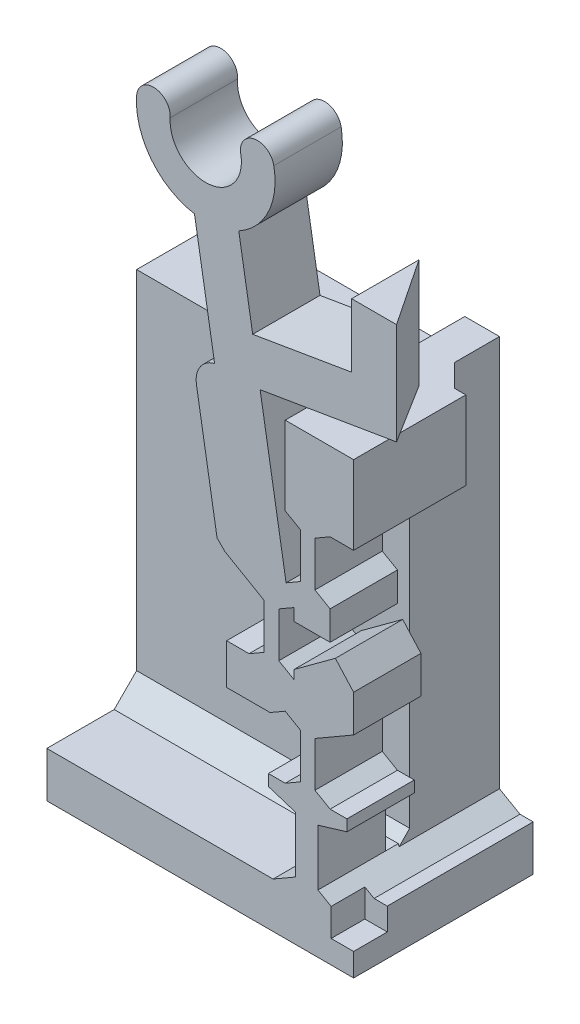
SolidWorks part; units mm, degrees
ref_plane "Front Plane" through (0, 0, 0) normal (0, 0, 1) x (1, 0, 0)
ref_plane "Top Plane" through (0, 0, 0) normal (0, 1, 0) x (1, 0, 0)
ref_plane "Right Plane" through (0, 0, 0) normal (1, 0, 0) x (0, 0, -1)
sketch "Sketch-SkeletonConfigUp" plane through (0, 0, 0) normal (0, 0, 1) x (1, 0, 0)
  line L0 (0, 0) -> (0, -50000) construction
  line L1 (0, 0) -> (4.5811, 6.2164) construction
  line L2 (9.8143, 13.3177) -> (4.5811, 13.945) construction
  line L3 (4.5811, 13.945) -> (2.9713, 10.4094) construction
  line L4 (2.9713, 10.4094) -> (4.5811, 6.2164) construction
  line L5 (4.5811, 13.945) -> (6.2429, 19.1409) construction
  line L6 (2.9713, 10.4094) -> (0.0405, 27.8193) construction
  line L7 (4.5811, 6.2164) -> (9.8143, 13.3177) construction
  line L8 (-587.3593, -797.0242) -> (9.8143, 13.3177) construction
  dimension "D2" = 7.7221
  dimension "D3" = 8.8212
  dimension "D4" = 5.2707
  dimension "D5" = 119.553
  dimension "D6" = 3.8848
  dimension "D7" = 5.4552
  dimension "D8" = 17.6549
  dimension "D9" = 4.4914
  dimension "D10" = 6.745
  dimension "D11" = 145.964
  dimension "D12" = 143.612
sketch "Sketch-SkeletonConfigDown" plane through (0, 0, 0) normal (0, 0, 1) x (1, 0, 0)
  line L0 (0, 0) -> (0, -50000) construction
  line L1 (0, 0) -> (4.5811, 6.2164) construction
  line L2 (9.8143, 13.3177) -> (4.5811, 13.945) construction
  line L3 (4.5811, 13.945) -> (6.1909, 10.4094) construction
  line L4 (6.1909, 10.4094) -> (4.5811, 6.2164) construction
  line L5 (4.5811, 13.945) -> (1.753, 18.6098) construction
  line L6 (6.1909, 10.4094) -> (-8.8652, 19.6294) construction
  line L7 (4.5811, 6.2164) -> (9.8143, 13.3177) construction
  line L8 (-589.9357, -800.5203) -> (9.8143, 13.3177) construction
  dimension "D2" = 7.7221
  dimension "D3" = 8.8212
  dimension "D4" = 5.2707
  dimension "D5" = 119.553
  dimension "D6" = 3.8848
  dimension "D7" = 5.4552
  dimension "D8" = 17.6549
  dimension "D9" = 4.4914
  dimension "D10" = 6.745
  dimension "D11" = 145.964
  dimension "D1" = 143.612
ref_plane "Plane-Cam Base" through (9.128, 0, 0) normal (1, 0, 0) x (0, 0, -1)
ref_plane "Plane-Down-to-Up Derailleur Clearance" through (6.628, 0, 0) normal (1, 0, 0) x (0, 0, -1)
ref_plane "Plane-Cam Cavity Roof" through (5.128, 0, 0) normal (1, 0, 0) x (0, 0, -1)
sketch "Sketch-SwitchBossUp" plane through (0, 0, 0) normal (0, 0, 1) x (1, 0, 0)
  line L0 (3.5811, 11.4759) -> (3.5811, 12.945) construction
  line L2 (6.5405, 22.165) -> (6.5405, 25.0005)
  line L3 (6.5405, 25.0005) -> (8.5405, 25.0005)
  line L4 (8.5405, 25.0005) -> (8.5405, 20.4736)
  line L5 (5.5811, 12.5552) -> (5.5811, 11.263)
  line L7 (1.5115, 25.1048) -> (2.1313, 21.4228)
  line L8 (-0.4607, 24.7728) -> (0.4359, 19.4465)
  line L9 (2.9713, 10.4094) -> (0.0405, 27.8193) construction
  line L11 (-0.0396, 22.2712) -> (1.9326, 22.6032) construction
  line L15 (6.628, -23.7286) -> (6.628, 23.7286) construction
  line L16 (2.9713, 10.4094) -> (4.5811, 6.2164) construction
  line L17 (3.5811, 12.945) -> (3.5811, 14.945) construction
  line L18 (5.5811, 12.945) -> (5.5811, 14.945) construction
  line L19 (4.2561, 13.945) -> (4.9061, 13.945) construction
  line L20 (3.5811, 14.945) -> (5.5811, 14.945) construction
  line L21 (3.5811, 12.945) -> (5.5811, 12.945) construction
  line L22 (4.5811, 12.945) -> (4.5811, 14.945) construction
  line L23 (4.5811, 6.2164) -> (8.5405, 7.1023) construction
  line L24 (1.9713, 9.4094) -> (1.9713, 11.4094) construction
  line L25 (3.9713, 9.4094) -> (3.9713, 11.4094) construction
  line L26 (3.9713, 9.4094) -> (1.9713, 9.4094) construction
  line L27 (1.9713, 11.4094) -> (3.9713, 11.4094) construction
  line L28 (3.5811, 7.2164) -> (5.5811, 7.2164) construction
  line L29 (3.5811, 7.2164) -> (3.5811, 5.2164) construction
  line L30 (5.5811, 7.2164) -> (5.5811, 5.2164) construction
  line L31 (3.5811, 5.2164) -> (5.5811, 5.2164) construction
  line L32 (4.9061, 6.2164) -> (4.2561, 6.2164) construction
  line L40 (3.2963, 10.4094) -> (2.6463, 10.4094) construction
  line L43 (2.874, 4.5093) -> (0.7934, 4.5093) construction
  line L46 (5.0405, 1.437) -> (5.0405, 3.937)
  line L51 (6.5405, 22.165) -> (2.1313, 21.4228)
  line L66 (0.0405, 27.8193) -> (0.0405, 50027.8193) construction
  line L74 (0.5455, 12.7717) -> (-0.3728, 18.2264)
  line L75 (0.3841, 13.7302) -> (2.3564, 14.0622) construction
  line L76 (5.5811, 11.263) -> (5.5811, 12.5552) construction
  line L77 (5.5811, 7.6061) -> (6.628, 8.2105)
  line L80 (5.8152, 10.763) -> (6.628, 9.8603)
  line L81 (8.5405, 7.9632) -> (8.5405, -49992.0368) construction
  line L82 (2.1313, 21.4228) -> (3.5585, 12.945) construction
  line L83 (3.6203, 12.5779) -> (2.4634, 19.4505)
  line L84 (2.4634, 19.4505) -> (8.5405, 20.4736)
  line L85 (6.9307, 9.5241) -> (8.5405, 7.7363) construction
  line L88 (3.5811, 18.8347) -> (6.8573, 18.8347)
  line L92 (3.7762, 8.3129) -> (6.9307, 9.5241) construction
  line L93 (6.3311, 4.3267) -> (5.0405, 3.937)
  line L95 (2.1313, 21.4228) -> (2.4634, 19.4505) construction
  line L96 (2.2974, 20.4367) -> (8.5405, 21.4876) construction
  line L97 (2.2974, 20.4367) -> (1.3112, 20.2707) construction
  line L98 (1.9713, 9.0197) -> (0.9713, 9.0197)
  line L99 (0.9713, 9.0197) -> (0.9713, 7.2164)
  line L100 (0.9713, 7.2164) -> (2.9061, 7.2164)
  line L101 (4.5811, 6.2164) -> (6.9307, 9.5241) construction
  line L104 (6.9307, 9.5241) -> (8.5405, 7.7363) construction
  line L106 (15.3091, 14.945) -> (5.5811, 14.945) construction
  line L107 (1.9713, 9.4094) -> (1.9713, 9.0197) construction
  line L111 (6.628, 9.8603) -> (6.628, 8.2105)
  line L112 (6.628, 9.8603) -> (6.9307, 9.5241) construction
  line L113 (2.8311, 4.8267) -> (2.8311, 4.3267)
  line L114 (7.3693, 7.7363) -> (7.3563, 7.7363) construction
  line L115 (6.8573, 18.8347) -> (15.3091, 18.8347)
  line L116 (15.3091, 18.8347) -> (15.3091, -1.1653)
  line L117 (15.3091, -1.1653) -> (5.0405, -1.1653)
  line L119 (10.4375, 14.0252) -> (10.4375, 2.1692)
  line L121 (5.0405, -1.1653) -> (5.0405, 1.437) construction
  line L122 (10.1044, 15.3031) -> (12.7068, 15.3031) construction
  line L123 (12.7068, 15.3031) -> (15.3091, 15.3031) construction
  line L124 (10.4375, 2.1692) -> (9.128, 0.8597)
  line L125 (8.5405, 8.8347) -> (15.3091, 8.8347) construction
  line L127 (5.5811, 15.3347) -> (5.5811, 14.945) construction
  line L130 (6.0405, 0.8597) -> (9.128, 0.8597)
  line L132 (2.8311, 4.3267) -> (4.0405, 3.937)
  line L133 (2.9713, 10.4094) -> (6.1909, 10.4094) construction
  line L134 (4.5811, 10.4094) -> (4.5811, 13.945) construction
  line L135 (4.5811, 10.4094) -> (4.5811, 6.2164) construction
  line L136 (0.8973, 12.4192) -> (0.5455, 12.7717)
  line L137 (3.9713, 9.4094) -> (5.5811, 7.2164) construction
  line L139 (5.8152, 10.763) -> (3.9713, 9.4094)
  line L140 (4.0405, 3.937) -> (4.0405, 1.437)
  line L141 (4.0405, 1.437) -> (3.0405, 0.8597)
  line L142 (3.0405, 0.8597) -> (3.0405, -1.1653)
  line L147 (5.5811, 11.263) -> (5.5811, 12.5552) construction
  line L149 (6.3311, 4.8267) -> (6.3311, 4.3267)
  line L150 (3.0405, -1.1653) -> (5.0405, -1.1653)
  line L151 (4.0405, 3.937) -> (5.0405, 3.937) construction
  line L152 (4.2561, 14.945) -> (4.2561, 12.945)
  line L153 (4.9061, 14.945) -> (4.9061, 12.945)
  line L155 (4.2561, 14.945) -> (3.5811, 15.3347)
  line L156 (4.9061, 14.945) -> (5.5811, 15.3347)
  line L157 (3.5811, 18.8347) -> (3.5811, 15.3347)
  line L158 (5.5811, 15.3347) -> (9.128, 15.3347)
  line L162 (3.2963, 11.4094) -> (3.2963, 9.4094)
  line L164 (2.6463, 11.4094) -> (2.6463, 9.4094)
  line L169 (4.2561, 7.2164) -> (4.2561, 5.2164)
  line L170 (4.9061, 5.2164) -> (4.9061, 7.2164)
  line L175 (4.2561, 7.2164) -> (3.5811, 7.6061)
  line L176 (4.9061, 7.2164) -> (5.5811, 7.6061)
  line L177 (5.5811, 7.2164) -> (5.5811, 7.6061) construction
  line L179 (4.2561, 5.2164) -> (3.5811, 4.8267)
  line L180 (3.5811, 5.2164) -> (3.5811, 4.8267) construction
  line L181 (3.5811, 4.8267) -> (2.8311, 4.8267)
  line L183 (4.9061, 5.2164) -> (5.5811, 4.8267)
  line L184 (5.5811, 5.2164) -> (5.5811, 4.8267) construction
  line L186 (9.128, -23.7286) -> (9.128, 23.7286) construction
  line L187 (2.6463, 9.4094) -> (1.9713, 9.0197)
  line L188 (3.2963, 9.4094) -> (3.9713, 9.0197)
  line L189 (3.2963, 11.4094) -> (3.9713, 11.7991)
  line L190 (2.6463, 11.4094) -> (0.8973, 12.4192)
  line L191 (3.9713, 11.4094) -> (3.9713, 11.7991) construction
  line L192 (3.9713, 11.7991) -> (3.9713, 11.263)
  line L193 (4.9061, 12.945) -> (5.5811, 12.5552)
  line L194 (4.2561, 12.945) -> (3.6203, 12.5779)
  line L195 (3.9713, 11.263) -> (5.5811, 11.263)
  line L196 (3.9713, 9.4094) -> (3.9713, 9.0197)
  line L197 (3.5811, 7.2164) -> (3.5811, 7.6061) construction
  line L199 (3.5811, 7.6061) -> (2.9061, 7.2164)
  line L200 (5.5811, 4.8267) -> (6.3311, 4.8267)
  line L201 (2.8311, 4.3267) -> (2.8311, 3.937) construction
  line L202 (2.8311, 3.937) -> (4.0405, 3.937) construction
  line L203 (10.4375, 14.0252) -> (9.128, 15.3347)
  line L204 (4.0405, 1.437) -> (3.0405, 1.437) construction
  line L205 (3.0405, 1.437) -> (3.0405, 0.8597) construction
  line L206 (5.0405, 1.437) -> (6.0405, 0.8597)
  arc A0 (1.5115, 25.1048) -> (3.0732, 28.3984) centre (0.0405, 27.8193) ccw
  arc A1 (-0.4607, 24.7728) -> (-3.038, 28.055) centre (0.0405, 27.8193) cw
  arc A2 (-3.038, 28.055) -> (-1.5424, 27.9405) centre (-2.2902, 27.9977) cw
  arc A3 (3.0732, 28.3984) -> (1.5998, 28.1171) centre (2.3365, 28.2577) ccw
  arc A4 (-1.5424, 27.9405) -> (1.5998, 28.1171) centre (0.0405, 27.8193) ccw
  arc A5 (3.5811, 12.945) -> (3.5811, 14.945) centre (3.1778, 13.945) ccw construction
  arc A6 (5.5811, 12.945) -> (5.5811, 14.945) centre (5.9843, 13.945) cw construction
  arc A7 (2.5293, 9.921) -> (1.9713, 11.4094) centre (1.568, 10.4094) ccw construction
  arc A8 (3.9713, 11.4094) -> (3.9713, 9.4094) centre (4.3745, 10.4094) ccw construction
  arc A9 (3.5811, 7.2164) -> (3.5811, 5.2164) centre (3.1779, 6.2164) cw construction
  arc A10 (5.5811, 7.2164) -> (5.5811, 5.2164) centre (5.9844, 6.2164) ccw construction
  arc A19 (-0.3728, 18.2264) -> (0.4359, 19.4465) centre (0.6836, 18.4042) cw
  arc A29 (1.9713, 9.4094) -> (2.5293, 9.921) centre (1.568, 10.4094) ccw construction
  point P53 (4.5811, 13.945)
  point P63 (2.9713, 10.4094)
  point P93 (0.9465, 22.4372)
  dimension "D23" = 1.5875
  dimension "D24" = 0.75
  dimension "D2" = 2
  dimension "D3" = 2
  dimension "D5" = 2
  dimension "D6" = 0.65
  dimension "D8" = 42
  dimension "D7" = 2
  dimension "D10" = 5
  dimension "D11" = 8.5
  dimension "D14" = 10
  dimension "D4" = 3
  dimension "D16" = 42
  dimension "D12" = 1
  dimension "D13" = 2.5
  dimension "D25" = 120
  dimension "D26" = 120
  dimension "D27" = 120
  dimension "D28" = 120
  dimension "D29" = 120
  dimension "D30" = 120
  dimension "D31" = 120
  dimension "D32" = 120
  dimension "D33" = 120
  dimension "D34" = 120
  dimension "D35" = 120
  dimension "D36" = 120
  dimension "D17" = 0.5
  dimension "D20" = 3.5
  dimension "D21" = 3.5
  dimension "D18" = 45
  dimension "D9" = 20
  dimension "D22" = 1
  dimension "D19" = 120
  dimension "D37" = 120
  dimension "D15" = 45
  dimension "D38" = 2
  dimension "D39" = 0.5
  dimension "D40" = 60
  dimension "D41" = 1
extrude "Boss-SwitchMain" add sketch "Sketch-SwitchBossUp" along normal blind 3
sketch "Sketch1" plane through (0, 0, 0) normal (0, 0, -1) x (-1, 0, 0)
  line L0 (-3.5811, 18.8347) -> (-3.5811, 15.3347) construction
  line L1 (-7.5811, -1.1653) -> (0.4122, -1.1653)
  line L2 (-7.5811, -1.1653) -> (-7.5811, 0.8597)
  line L4 (0.4122, -1.1653) -> (0.4122, 0.8597)
  line L5 (-3.5811, 18.8347) -> (-7.5811, 18.8347)
  line L10 (-7.5811, 18.8347) -> (-7.5811, 15.3347)
  line L11 (-4.0405, 1.437) -> (-5.0405, 1.437)
  line L12 (-7.5811, 15.3347) -> (-3.5811, 15.3347)
  line L13 (-4.0405, 1.437) -> (-3.0405, 0.8597)
  line L14 (-3.5811, 15.3347) -> (-3.5811, 18.8347)
  line L20 (-6.8573, 18.8347) -> (-15.3091, 18.8347) construction
  line L22 (-3.0405, -1.1653) -> (-15.3091, -1.1653) construction
  line L23 (-3.0405, 0.8597) -> (0.4122, 0.8597)
  line L24 (-5.0405, 1.437) -> (-6.0405, 0.8597)
  line L25 (-6.0405, 0.8597) -> (-7.5811, 0.8597)
  dimension "D4" = 4
extrude "Boss-Flange Width" add sketch "Sketch1" along normal blind 5
ref_plane "Plane-Sta2Sit Groove" through (0.0405, 0, 0) normal (1, 0, 0) x (0, 0, -1)
ref_plane "Plane-Cam Outer Surface" through (-12.0395, 0, 0) normal (1, 0, 0) x (0, 0, -1)
ref_plane "Plane-FlangeTop" through (-7.0395, 0, 0) normal (1, 0, 0) x (0, 0, -1)
sketch "Sketch2" plane through (-7.0395, 0, 0) normal (1, 0, 0) x (0, 0, -1)
  line L0 (5, 15.3347) -> (0, 15.3347) construction
  line L1 (5, 17.3347) -> (1, 17.3347)
  line L2 (5, 17.3347) -> (5, 15.3347)
  line L3 (5, 15.3347) -> (1, 15.3347)
  line L4 (1, 17.3347) -> (1, 15.3347)
  line L10 (-3, -1.1653) -> (-3, 18.8347) construction
  line L11 (5, 0.8597) -> (-3, 0.8597)
  line L12 (5, 0.8597) -> (5, -1.1653)
  line L13 (5, -1.1653) -> (-3, -1.1653)
  line L14 (-3, 0.8597) -> (-3, -1.1653)
  line L15 (0, 10.4094) -> (0, 27.8193) construction
  line L17 (5, 0.8597) -> (5, -1.1653) construction
  line L18 (-3, 0.8597) -> (0, 0.8597) construction
  dimension "D1" = 1
  dimension "D2" = 2
extrude "Boss-Flange Height" add sketch "Sketch2" along normal up to surface (11.6675 mm away)
sketch "Sketch10" plane through (0, 18.8347, 0) normal (0, 1, 0) x (1, 0, 0)
  line L1 (7.5811, 5) -> (5.128, 5)
  line L2 (7.5811, 5) -> (7.5811, 2)
  line L3 (7.5811, 2) -> (5.128, 2)
  line L5 (4.628, 7) -> (4.628, 1) construction
  line L6 (3.5811, 1) -> (-7.0395, 1) construction
  line L8 (5.128, 5) -> (5.128, 2)
  dimension "D1" = 1
extrude "Cut-Up-To-Down Derailleur Clearance" cut sketch "Sketch10" against normal up to next
sketch "Sketch17" plane through (0, 15.3347, 0) normal (0, -1, 0) x (1, 0, 0)
  line L0 (5.128, -5) -> (-7.0395, -5)
  line L1 (5.128, -5) -> (-7.0395, -5) construction
  line L2 (-7.0395, -5) -> (-7.0395, -1)
  line L3 (-7.0395, -1) -> (5.128, -1)
  line L4 (5.128, -1) -> (5.128, -5)
  line L5 (-7.0395, -1) -> (-7.0395, -5) construction
extrude "Boss-Flange Support" add sketch "Sketch17" along normal up to surface (14.475 mm away) up to face at (-1.9995, 0.8597, -1)
sketch "Sketch-HolePositions" plane through (0, -1.1653, 0) normal (0, -1, 0) x (1, 0, 0)
  line L0 (-7.0395, -3) -> (7.5811, -3) construction
  line L1 (7.5811, -5) -> (-7.0395, -5) construction
  line L2 (7.5811, -5) -> (7.5811, 0) construction
  line L4 (-7.0395, -22.2167) -> (-7.0395, 22.2167) construction
  line L5 (3.5811, -1) -> (3.5811, -5) construction
  point P6 (-4.0395, -3)
  point P7 (0.5811, -3)
  dimension "D1" = 3
  dimension "D2" = 3
  dimension "D3" = 2
sketch "Sketch6" plane through (0, -1.1653, 0) normal (0, -1, 0) x (-1, 0, 0)
  point P0 (4.0395, 3)
  point P3 (-0.5811, 3)
hole_wizard "Tap Drill for M2x0.4 Tap1" positions "Sketch6" profile "Sketch5" hole size "M2x0.4" standard "ANSI Metric" end condition through all
sketch "Sketch5" plane through (-4.0395, -1.1653, -3) normal (1, 0, 0) x (0, 0, -1)
  line L0 (0, 0) -> (0, 30.1731)
  line L1 (0, 30.1731) -> (0.8, 30.1731)
  line L2 (0.8, 30.1731) -> (0.8, 0)
  line L5 (0.8, 0) -> (0, 0)
  line L11 (0, -6.35) -> (0, 107.95) construction
  dimension "Thru Hole Dia." = 1.6
  dimension "Thru Hole Depth" = 30.1731
sketch "Sketch9" plane through (0, -1.1653, 0) normal (0, -1, 0) x (1, 0, 0)
  point P0 (-4.0395, -3)
  point P3 (0.5811, -3)
hole_wizard "M2 Clearance Hole2" positions "Sketch9" profile "Sketch8" hole size "M2" standard "ANSI Metric"
sketch "Sketch8" plane through (-4.0395, -1.1653, -3) normal (1, 0, 0) x (0, 0, -1)
  line L0 (0, 0) -> (0, 15.721)
  line L1 (0, 15.721) -> (1.2, 15)
  line L2 (1.2, 15) -> (1.2, 0)
  line L5 (1.2, 0) -> (0, 0)
  line L10 (0, 15.721) -> (-1.2, 15) construction
  line L11 (0, -6.35) -> (0, 107.95) construction
  dimension "Hole Dia." = 2.4
  dimension "Hole Depth" = 15
  dimension "Drill Angle" = 118
sketch "Sketch-Measurements for Derailleur Ramps" plane through (0, 0, 0) normal (0, 0, 1) x (1, 0, 0)
  line L0 (2.4634, 19.4505) -> (2.1313, 21.4228)
  line L1 (2.2974, 20.4367) -> (1.3112, 20.2707)
  line L2 (2.9713, 10.4094) -> (0.0405, 27.8193) construction
  line L3 (1.3112, 20.2707) -> (-4.0257, 16.6658)
  line L4 (6.1909, 10.4094) -> (-8.8652, 19.6294) construction
  line L5 (1.3112, 20.2707) -> (2.6012, 12.6077)
  line L6 (2.6012, 12.6077) -> (-4.0257, 16.6658)
  line L7 (-1.3573, 18.4682) -> (-1.3573, 20.2707)
  line L8 (-1.3573, 20.2707) -> (1.3112, 20.2707)
  line L9 (6.1909, 10.4094) -> (2.9713, 10.4094)
  line L10 (5.386, 8.3129) -> (3.7762, 8.3129)
  line L12 (6.1909, 10.4094) -> (4.5811, 6.2164) construction
  line L13 (4.5811, 8.3129) -> (4.5811, 8.7912)
  line L14 (4.5811, 6.2164) -> (5.386, 8.3129)
  line L15 (2.9713, 10.4094) -> (4.5811, 6.2164) construction
  line L16 (3.7762, 8.3129) -> (4.5811, 6.2164)
  line L17 (5.386, 8.3129) -> (5.386, 8.7912)
  dimension "D1" = 2.6685
  dimension "D2" = 0.8049
sketch "Sketch12" plane through (0, 25.0005, 0) normal (0, 1, 0) x (1, 0, 0)
  line L0 (6.5405, 0) -> (8.5405, -3)
  line L1 (8.5405, -3) -> (8.5405, 0)
  line L2 (8.5405, 0) -> (6.5405, 0)
extrude "Cut-Up-to-Down Cantilever Slope" cut sketch "Sketch12" against normal up to next
ref_plane "Plane1" through (0, 7.1023, 0) normal (0, 1, 0) x (1, 0, 0)
sketch "Sketch-Derailleur Location" plane through (0, 7.1023, 0) normal (0, 1, 0) x (1, 0, 0)
  line L0 (8.5405, 0) -> (8.5405, -3)
  line L1 (4.0405, -3) -> (3.0405, -3) construction
  line L2 (-119237.4187, 0) -> (9.8143, 0) construction
  point P0 (8.5405, 0)
  point P8 (8.5405, -1.5)
ref_plane "Plane-Cantilever Cut" [suppressed] through (7.0848, 8.5204, -1.9058) normal (-0.6301, -0.7578, 0.1695) x (-0.7765, 0.6151, -0.1368)
sketch "Sketch14" [suppressed] plane through (7.0848, 8.5204, -1.9058) normal (-0.6301, -0.7578, 0.1695) x (-0.7765, 0.6151, -0.1368)
  line L0 (2.3023, -1.6911) -> (-0.3551, -1.6911)
  line L2 (2.3023, -4.3362) -> (2.3023, -1.6911)
  line L3 (-0.3551, -1.6911) -> (-0.3551, -4.4608)
  line L5 (-0.3551, -4.4608) -> (1.0087, -5.0843)
  line L6 (1.0087, -5.0843) -> (2.3023, -4.3362)
extrude "Cut-Down-to-Up Cantilever Slope" [suppressed] cut sketch "Sketch14" against normal up to next
sketch "Sketch16" plane through (0, 0, 0) normal (0, 0, -1) x (-1, 0, 0)
  line L0 (-6.628, 18.8347) -> (-15.3091, 18.8347)
  line L1 (-15.3091, 18.8347) -> (-15.3091, -1.1653)
  line L2 (-15.3091, -1.1653) -> (-6.628, -1.1653)
  line L3 (-15.3091, -1.1653) -> (-5.0405, -1.1653) construction
  line L4 (-6.628, -1.1653) -> (-6.628, 5.2038)
  line L5 (-6.628, 5.2038) -> (-8.0037, 5.2038)
  line L6 (-8.0037, 5.2038) -> (-8.0037, 12.0484)
  line L7 (-8.0037, 12.0484) -> (-6.628, 12.0484)
  line L8 (-6.628, 12.0484) -> (-6.628, 18.8347)
  line L9 (-6.628, 23.7286) -> (-6.628, -23.7286) construction
extrude "Cut-Down-to-Up Derailleur Clearance" cut sketch "Sketch16" against normal through all and the other way through all
ref_plane "Plane-Symmetry Plane" through (0, 0, 1.5) normal (0, 0, 1) x (1, 0, 0)
sketch "Sketch-Cable Center Point" plane through (0, 0, 1.5) normal (0, 0, 1) x (1, 0, 0)
  line L0 (0.0405, 27.8193) -> (0.1722, 27.0366)
  line L1 (2.9713, 10.4094) -> (0.0405, 27.8193) construction
  point P0 (0.0405, 27.8193)
  dimension "D1" = 0.7937
chamfer "Chamfer-Flange Support" distance 1.5 angle 45 1 edges at (3.5811, 17.3347, -3)
chamfer "Chamfer-Flange Support 2" distance 1 angle 45 2 edges at (5.128, 17.0847, -2) (5.128, 15.3347, -1.5)
chamfer "Chamfer-Flange Support 3" distance 1 angle 45 1 edges at (-1.9995, 0.8597, -1)
sketch "Sketch18" plane through (6.628, 0, 0) normal (1, 0, 0) x (0, 0, -1)
  line L1 (-3, -0.1403) -> (-1.5, -0.1403)
  line L2 (-3, -0.1403) -> (-3, 1.437)
  line L3 (-3, 1.437) -> (-1.5, 1.437)
  line L4 (-1.5, -0.1403) -> (-1.5, 1.437)
  line L5 (0.5774, 1.437) -> (0, 1.437) construction
  line L6 (-3, -1.1653) -> (-3, 0.8597) construction
  line L7 (-3, 0.8597) -> (5, 0.8597) construction
  dimension "D1" = 1.5
  dimension "D2" = 1
extrude "Cut-Down-to-Up Derailleur Clearance 2" cut sketch "Sketch18" against normal blind 1
equation "\"axle-diameter\"=2"
equation "\"switch-thickness\"=12"
equation "\"base-width\"=4.0"
equation "\"axle-bushing-radius\"=3"
equation "\"clearance\"= 0.25"
equation "\"arm-width\"=1.5"
equation "\"min-diameter\"=70"
equation "\"alpha\"=143.6120"
equation "\"gamma\"=119.5526"
equation "\"delta\"=145.9637"
equation "\"epsilon\"=6.7452"
equation "\"l_AB\"=8.8212"
equation "\"l_AC\"=4.4914"
equation "\"l_BD\"=5.2707"
equation "\"l_CD\"=3.8848"
equation "\"l_CE\"=17.6549"
equation "\"l_DF\"=5.4552"
equation "\"l_OA\"=7.7221"
equation "\"D2@Sketch-SkeletonConfigUp\" = \"l_OA\""
equation "\"D3@Sketch-SkeletonConfigUp\" = \"l_AB\""
equation "\"D4@Sketch-SkeletonConfigUp\" = \"l_BD\""
equation "\"D5@Sketch-SkeletonConfigUp\" = \"gamma\""
equation "\"D6@Sketch-SkeletonConfigUp\" = \"l_CD\""
equation "\"D7@Sketch-SkeletonConfigUp\" = \"l_DF\""
equation "\"D8@Sketch-SkeletonConfigUp\" = \"l_CE\""
equation "\"D9@Sketch-SkeletonConfigUp\" = \"l_AC\""
equation "\"D_groove\"=3.175"
equation "\"D7@Sketch-SkeletonConfigDown\" = \"l_DF\""
equation "\"D6@Sketch-SkeletonConfigDown\" = \"l_CD\""
equation "\"D2@Sketch-SkeletonConfigDown\" = \"l_OA\""
equation "\"D3@Sketch-SkeletonConfigDown\" = \"l_AB\""
equation "\"D9@Sketch-SkeletonConfigDown\" = \"l_AC\""
equation "\"D8@Sketch-SkeletonConfigDown\" = \"l_CE\""
equation "\"D5@Sketch-SkeletonConfigDown\" = \"gamma\""
equation "\"D4@Sketch-SkeletonConfigDown\" = \"l_BD\""
equation "\"D1@Sketch-SkeletonConfigDown\" = \"alpha\""
equation "\"hinge_length\"=1.5"
equation "\"hinge_depth\"=0.25"
equation "\"D10@Sketch-SkeletonConfigUp\"=\"epsilon\""
equation "\"D11@Sketch-SkeletonConfigUp\"=\"delta\""
equation "\"D12@Sketch-SkeletonConfigUp\"=\"alpha\""
equation "\"D11@Sketch-SkeletonConfigDown\"=\"delta\""
equation "\"D10@Sketch-SkeletonConfigDown\"=\"epsilon\""
equation "\"EE_dx\"=8.9056"
equation "\"EE_dy\"=8.1898"
equation "\"r_groove\"=\"D_groove\"/2"
equation "\"t_wall\"=25.4/16"
equation "\"width_lower\"=\"D_groove\"+\"t_wall\""
equation "\"cable_to_bottom\"=30.6257"
equation "\"switch_EE-up_base_dy\"=24"
equation "\"switch_EE-down_base_dy\"=16"
equation "\"D_axle\"=25.4/8"
equation "\"D_up_to_down\"=16"
equation "\"D_down_to_up\"=25"
equation "\"t_cam_base\"=7.5"
equation "\"D23@Sketch-SwitchBossUp\"=\"D_groove\"/2"
equation "\"D1@Sketch-Cable Center Point\"=\"D_groove\"/4"
